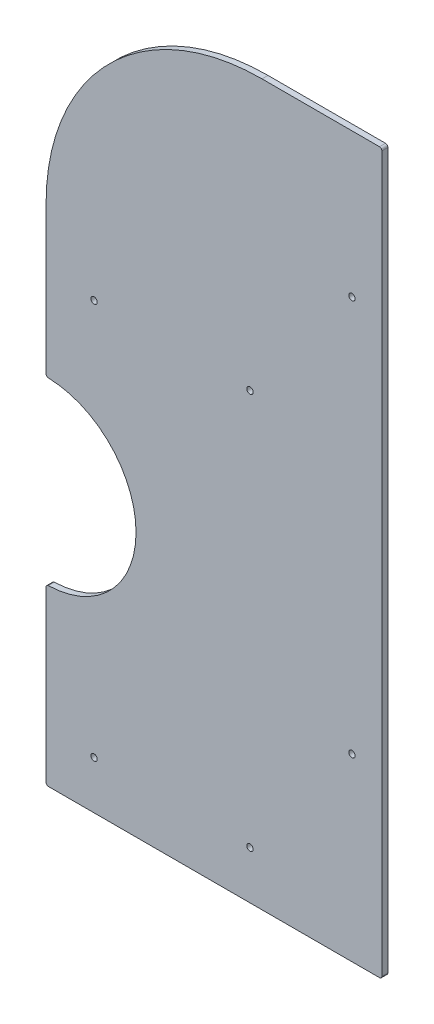
SolidWorks part; units mm, degrees
material "PE High Density"
ref_plane "Front Plane" through (0, 0, 0) normal (0, 0, 1) x (1, 0, 0)
ref_plane "Top Plane" through (0, 0, 0) normal (0, 1, 0) x (1, 0, 0)
ref_plane "Right Plane" through (0, 0, 0) normal (1, 0, 0) x (0, 0, -1)
sketch "Sketch1" plane through (0, 0, 0) normal (0, 0, 1) x (1, 0, 0)
  line L1 (-177.8, 381) -> (177.8, 381)
  line L2 (-177.8, 381) -> (-177.8, -381)
  line L3 (-177.8, -381) -> (177.8, -381)
  line L4 (177.8, 381) -> (177.8, -381)
  line L5 (-177.8, 381) -> (177.8, -381) construction
  line L6 (-177.8, -381) -> (177.8, 381) construction
  point P0 (0, 0)
  dimension "D1" = 762
  dimension "D2" = 355.6
extrude "Boss-Extrude1" add sketch "Sketch1" along normal blind 6.35
sketch "Sketch2" plane through (0, 0, 6.35) normal (0, 0, 1) x (1, 0, 0)
  line L0 (-177.8, -381) -> (177.8, -381) construction
  line L1 (-177.8, -381) -> (177.8, -381) construction
  line L3 (177.8, 381) -> (-177.8, 381) construction
  line L5 (-177.8, 381) -> (-177.8, -381) construction
  line L6 (177.8, 381) -> (177.8, -381) construction
  circle A0 centre (-127, -330.2) radius 16.7005
  circle A1 centre (146.05, -190.5) radius 16.7005
  circle A2 centre (-127, 88.9) radius 16.7005
  circle A3 centre (146.05, 228.6) radius 16.7005
  circle A4 centre (38.1, 88.9) radius 16.7005
  circle A5 centre (38.1, -330.2) radius 16.7005
  circle A6 centre (146.05, 228.6) radius 3.3734
  circle A7 centre (38.1, 88.9) radius 3.3734
  circle A8 centre (-127, 88.9) radius 3.3734
  circle A9 centre (146.05, -190.5) radius 3.3734
  circle A10 centre (38.1, -330.2) radius 3.3734
  circle A11 centre (-127, -330.2) radius 3.3734
  dimension "D3" = 33.401
  dimension "D6" = 33.401
  dimension "D8" = 33.401
  dimension "D12" = 33.401
  dimension "D13" = 33.401
  dimension "D17" = 33.401
  dimension "D16" = 6.7469
  dimension "D18" = 6.7469
  dimension "D19" = 6.7469
  dimension "D20" = 6.7469
  dimension "D21" = 6.7469
  dimension "D22" = 6.7469
  dimension "D1" = 50.8
  dimension "D2" = 469.9
  dimension "D4" = 50.8
  dimension "D5" = 31.75
  dimension "D7" = 152.4
  dimension "D9" = 50.8
  dimension "D10" = 190.5
  dimension "D11" = 31.75
  dimension "D14" = 165.1
  dimension "D15" = 165.1
fillet "Fillet1" radius 228.6 1 edges at (-177.8, 381, 3.175) type face fillet first side face at (-177.8, 0, 3.175) second side face at (0, 381, 3.175)
sketch "Sketch3" plane through (0, 0, 6.35) normal (0, 0, 1) x (1, 0, 0)
  line L0 (-177.8, 381) -> (-177.8, -381) construction
  circle A0 centre (-177.8, -101.6) radius 95.25
  dimension "D1" = 190.5
  dimension "D2" = 101.6
extrude "Cut-Extrude1" cut sketch "Sketch3" against normal through all
extrude "Cut-Extrude2" cut sketch "Sketch2" against normal through all contours A6 | A7 | A8 | A9 | A10 | A11
fillet "Fillet2" radius 2.54 5 edges at (-177.8, -6.35, 3.175) (-177.8, -196.85, 3.175) (-177.8, -381, 3.175) (177.8, -381, 3.175) (177.8, 381, 3.175)
